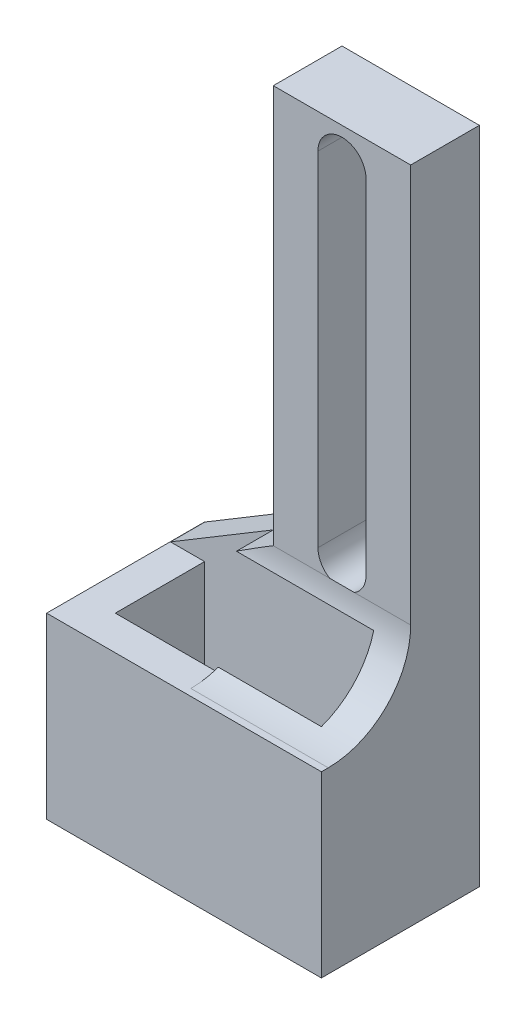
SolidWorks part; units mm, degrees
material "ABS PC"
ref_plane "Front Plane" through (0, 0, 0) normal (0, 0, 1) x (1, 0, 0)
ref_plane "Top Plane" through (0, 0, 0) normal (0, 1, 0) x (1, 0, 0)
ref_plane "Right Plane" through (0, 0, 0) normal (1, 0, 0) x (0, 0, -1)
sketch "Sketch1" plane through (0, 0, 0) normal (0, 0, 1) x (1, 0, 0)
  line L0 (0, 0) -> (0, 35)
  line L1 (0, 0) -> (10, 0)
  line L2 (0, 35) -> (10, 35)
  line L3 (10, 0) -> (10, 35)
  dimension "D1" = 35
  dimension "D2" = 10
extrude "Boss-Extrude1" add sketch "Sketch1" along normal blind 5
sketch "Sketch9" plane through (0, 0, 0) normal (0, -1, 0) x (1, 0, 0)
  line L0 (-10, 0) -> (10, 0)
  line L1 (-10, 0) -> (-10, 11.5)
  line L2 (10, 0) -> (10, 11.5)
  line L3 (-10, 11.5) -> (10, 11.5)
  line L4 (0, 5) -> (0, 0) construction
  point P0 (0, 2.5)
  dimension "D1" = 11.5
  dimension "D2" = 20
  dimension "D3" = 10
extrude "Boss-Extrude3" add sketch "Sketch9" along normal blind 13
fillet "Fillet1" radius 6 1 edges
sketch "Sketch10" plane through (0, -13, 0) normal (0, -1, 0) x (1, 0, 0)
  line L0 (-7.5, 2.5) -> (7.5, 2.5)
  line L1 (-7.5, 2.5) -> (-7.5, 9)
  line L2 (7.5, 2.5) -> (7.5, 9)
  line L3 (-7.5, 9) -> (7.5, 9)
  line L4 (-10, 11.5) -> (-10, 0) construction
  line L5 (-10, 0) -> (10, 0) construction
  dimension "D1" = 6.5
  dimension "D2" = 15
  dimension "D3" = 2.5
  dimension "D4" = 2.5
extrude "Cut-Extrude4" cut sketch "Sketch10" against normal blind 17.5
sketch "Sketch4" plane through (0, 0, 5) normal (0, 0, 1) x (1, 0, 0)
  line L0 (5, 32.5) -> (5, 7.5) construction
  line L1 (6.75, 32.5) -> (6.75, 7.5)
  line L2 (3.25, 32.5) -> (3.25, 7.5)
  line L3 (10, 35) -> (0, 35) construction
  line L4 (10, 6) -> (10, 35) construction
  arc A0 (6.75, 32.5) -> (3.25, 32.5) centre (5, 32.5) ccw
  arc A1 (3.25, 7.5) -> (6.75, 7.5) centre (5, 7.5) ccw
  point P2 (5, 20)
  dimension "D1" = 3.5
  dimension "D2" = 2.5
  dimension "D3" = 25
  dimension "D4" = 5
extrude "Cut-Extrude2" cut sketch "Sketch4" against normal blind 10
chamfer "Chamfer2" distance 6 angle 59 1 edges
